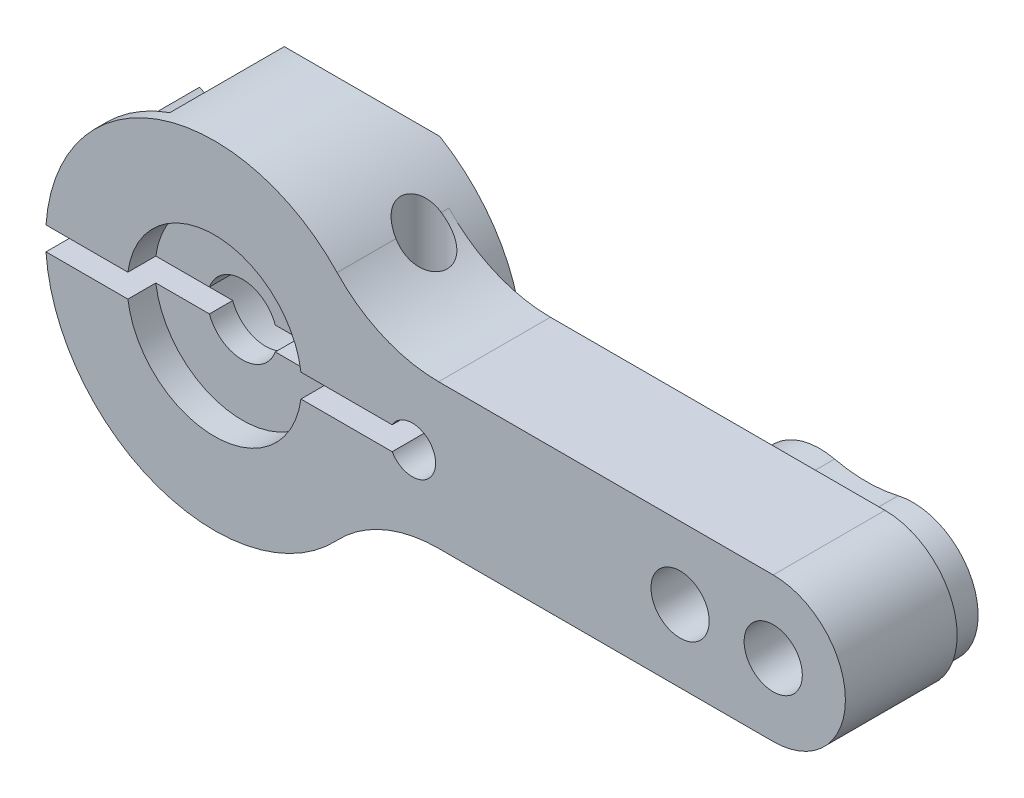
SolidWorks part; units mm, degrees
ref_plane "Спереди (XY)" through (0, 0, 0) normal (0, 0, 1) x (1, 0, 0)
ref_plane "Сверху (XZ)" through (0, 0, 0) normal (0, 1, 0) x (1, 0, 0)
ref_plane "Справа (ZY)" through (0, 0, 0) normal (1, 0, 0) x (0, 0, -1)
sketch "Эскиз1" plane through (0, 0, 0) normal (0, 0, 1) x (1, 0, 0)
  line L0 (24, 3.1) -> (6.5538, 3.1)
  line L1 (24, -3.1) -> (6.5538, -3.1)
  line L2 (24, 0) -> (20, 0) construction
  line L3 (1.4142, 0.5) -> (7.634, 0.5)
  line L4 (0, 0) -> (12.6344, 0) construction
  line L5 (1.4142, -0.5) -> (7.634, -0.5)
  line L6 (-1.4142, 0.5) -> (-7.2327, 0.5)
  line L7 (-1.4142, -0.5) -> (-7.2327, -0.5)
  circle A0 centre (0, 0) radius 1.5
  circle A1 centre (0, 0) radius 2.75
  circle A2 centre (0, 0) radius 7.25
  arc A3 (24, -3.1) -> (24, 3.1) centre (24, 0) ccw
  circle A4 centre (24, 0) radius 1.25
  arc A5 (23.3636, -2.7267) -> (23.3636, 2.7267) centre (24, 0) ccw
  circle A6 centre (20, 0) radius 1.25
  arc A7 (20.6364, 2.7267) -> (20.6364, -2.7267) centre (20, 0) ccw
  circle A8 centre (0, 0) radius 3.75
  arc A9 (20.6364, -2.7267) -> (23.3636, -2.7267) centre (22, -8.5697) cw
  arc A10 (20.6364, 2.7267) -> (23.3636, 2.7267) centre (22, 8.5697) ccw
  circle A11 centre (8.5, 0) radius 1
  dimension "D1" = 14.5
  dimension "D2" = 3
  dimension "D3" = 5.5
  dimension "D4" = 7.5
  dimension "D6" = 20
  dimension "D7" = 24
  dimension "D8" = 2.5
  dimension "D9" = 5.6
  dimension "D10" = 6
  dimension "D12" = 2
  dimension "D13" = 8.5
  dimension "D5" = 6.2
  dimension "D11" = 1
extrude "Бобышка-Вытянуть1" add sketch "Эскиз1" along normal blind 6 contours A11 L5 A2 L1 A3 L0 L3 A7 A10 A5 A9 | A10 A7 A9 A5 A6 A4 | A8 L3 A2 L6 | L3 A8 L6 A1 | L3 A1 L6 A0 | A8 L7 A2 L5 | L7 A8 L5 A1 | L7 A1 L5 A0 region at (13.7327, 0, 0) region at (0, 3.8269, 0) region at (0, -3.8269, 0) region at (0, 3.6689, 0) region at (0, 1.5952, 0) region at (-3.2103, -0.5811, 0) region at (0, -1.5952, 0) region at (22, 0, 0)
extrude "Вырез-Вытянуть1" cut sketch "Эскиз1<3>" along normal blind 1.2 contours A11 L5 A2 L1 A3 L0 L3 A7 A10 A5 A9 region at (13.7327, 0, 0)
sketch "Эскиз1<3>" plane through (0, 0, 0) normal (0, 0, 1) x (1, 0, 0) same geometry as "Эскиз1"
extrude "Вырез-Вытянуть2" cut sketch "Эскиз1<4>" along normal blind 3.8 contours A1
sketch "Эскиз1<4>" plane through (0, 0, 0) normal (0, 0, 1) x (1, 0, 0) same geometry as "Эскиз1"
extrude "Вырез-Вытянуть3" cut sketch "Эскиз1<5>" against normal blind 1.2 from surface contours A8 starting at face at (5.4057, 0, 6)
sketch "Эскиз1<5>" plane through (0, 0, 0) normal (0, 0, 1) x (1, 0, 0) same geometry as "Эскиз1"
fillet "Скругление1" radius 6 2 edges at (6.5538, -3.1, 3.6) (6.5538, 3.1, 3.6)
sketch "Эскиз2" plane through (0, 0, 0) normal (0, 0, 1) x (1, 0, 0)
  line L0 (0, 0) -> (-5.099, 5.5) construction
  line L1 (0, 0) -> (10.198, -11) construction
  line L2 (-2.7042, 0.5) -> (-7.2327, 0.5) construction
  circle A0 centre (5.099, -5.5) radius 3
  circle A1 centre (-5.099, 5.5) radius 3
  circle A2 centre (0, 0) radius 7.5 construction
  point P7 (-5.099, 2.5)
  dimension "D1" = 6
  dimension "D3" = 15
  dimension "D2" = 2
extrude "Вырез-Вытянуть4" cut sketch "Эскиз2" along normal blind 5.5
sketch "Эскиз3" plane through (0, 0, 0) normal (0, 1, 0) x (1, 0, 0)
  line L0 (0, 0) -> (0, -19.0596) construction
  line L1 (-7.2327, -6) -> (5.2697, -6) construction
  circle A0 centre (5.5, -2.5) radius 1
  circle A1 centre (-5.5, -2.5) radius 1
  dimension "D3" = 2
  dimension "D1" = 3.5
  dimension "D2" = 5.5
extrude "Вырез-Вытянуть5" cut sketch "Эскиз3" against normal through all both and the other way through all
sketch "Эскиз4" plane through (0, 0, 0) normal (1, 0, 0) x (0, 0, -1)
  line L0 (0, -6.25) -> (-1, -7.25)
  line L1 (-1, -7.25) -> (0, -7.25)
  line L2 (0, -7.25) -> (0, -6.25)
  line L3 (0, -7.25) -> (0, -0.5) construction
  line L4 (-6, -7.25) -> (0, -7.25) construction
  line L5 (0, 0) -> (12.563, 0) construction
  line L6 (0, 7.25) -> (0, 6.25)
  line L7 (-1, 7.25) -> (0, 7.25)
  line L8 (0, 6.25) -> (-1, 7.25)
  dimension "D1" = 1
extrude "Вырез-Вытянуть6" cut sketch "Эскиз4" against normal through all both and the other way through all
